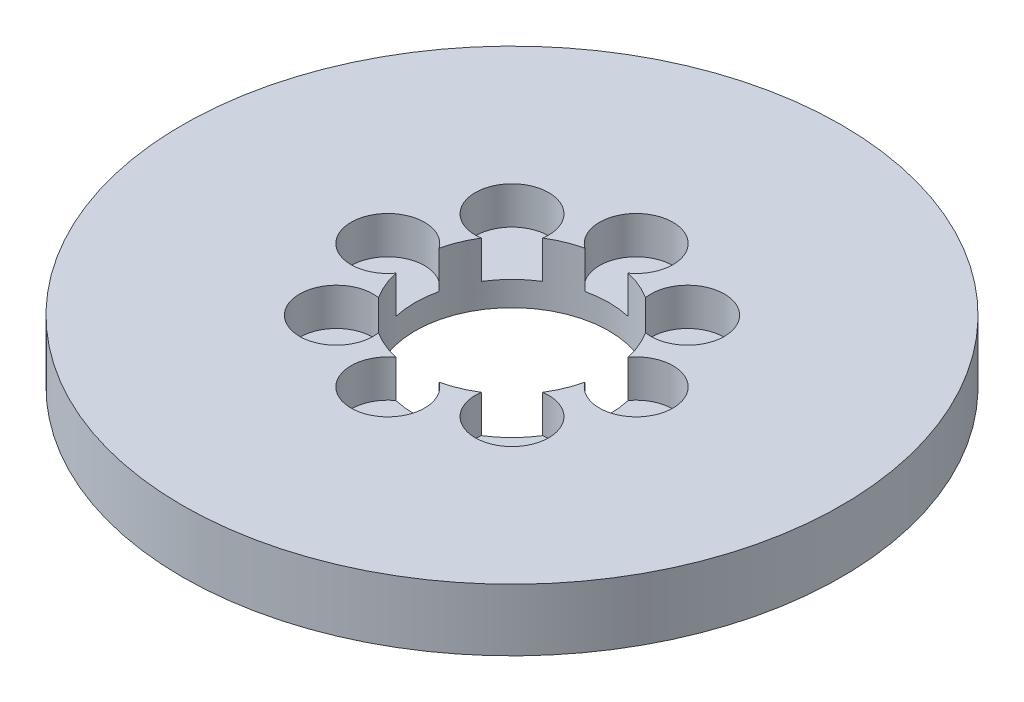
SolidWorks part; units mm, degrees
ref_plane "Front Plane" through (0, 0, 0) normal (0, 0, 1) x (1, 0, 0)
ref_plane "Top Plane" through (0, 0, 0) normal (0, 1, 0) x (1, 0, 0)
ref_plane "Right Plane" through (0, 0, 0) normal (1, 0, 0) x (0, 0, -1)
sketch "Sketch1" plane through (0, 0, 0) normal (0, 1, 0) x (1, 0, 0)
  circle A0 centre (0, 0) radius 85
  dimension "FLANGE_OD" = 170
extrude "Boss-Extrude1" add sketch "Sketch1" along normal blind 16
sketch "Sketch2" plane through (0, 0, 0) normal (0, 1, 0) x (1, 0, 0)
  circle A0 centre (0, 0) radius 25
  dimension "BORE_D" = 50
extrude "Cut-Extrude1" cut sketch "Sketch2" along normal through all
sketch "Sketch3" plane through (0, 16, 0) normal (0, 1, 0) x (1, 0, 0)
  circle A0 centre (0, 0) radius 32.031 construction
  circle A1 centre (-32.031, 0) radius 9.4819
  dimension "BOLT_D" = 18.9638
  dimension "BOLT_PCD" = 64.062
extrude "Cut-Extrude2" cut sketch "Sketch3" against normal blind 9.673
pattern_circular "CirPattern1" count 8 over 360 about axis through (0, 0, 0) along (0, 1, 0) of "Cut-Extrude2"
